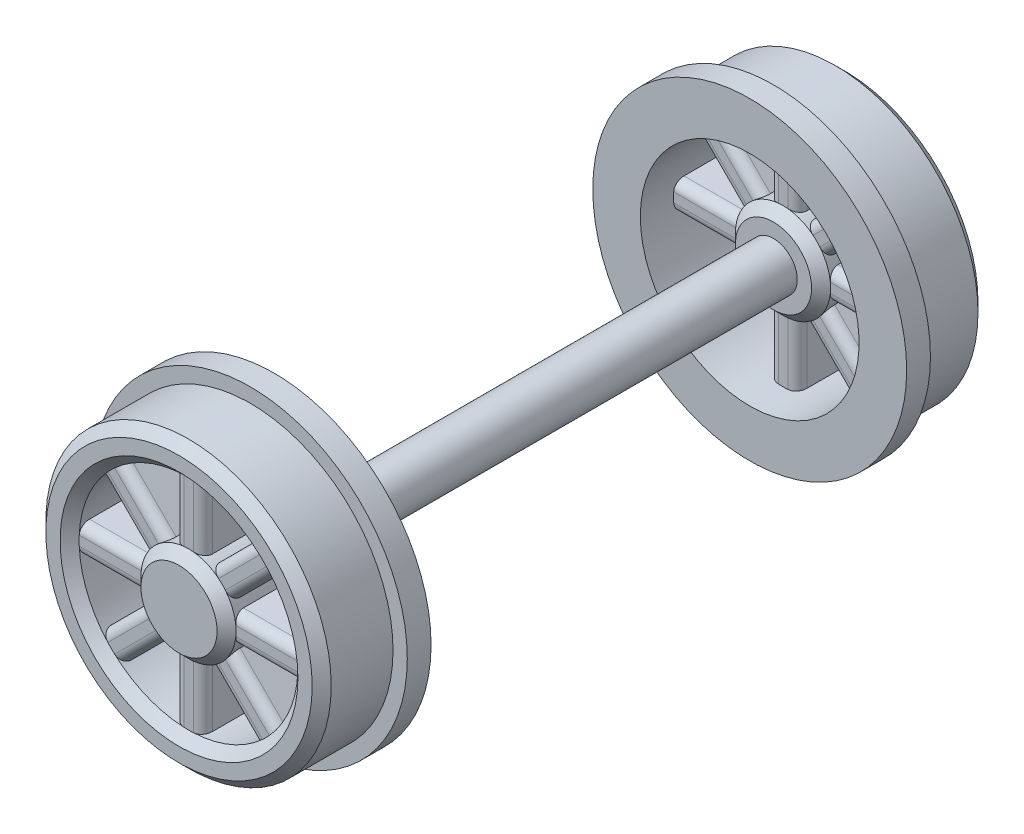
SolidWorks part; units mm, degrees
ref_plane "Front Plane" through (0, 0, 0) normal (0, 0, 1) x (1, 0, 0)
ref_plane "Top Plane" through (0, 0, 0) normal (0, 1, 0) x (1, 0, 0)
ref_plane "Right Plane" through (0, 0, 0) normal (1, 0, 0) x (0, 0, -1)
sketch "Master Sketch" plane through (0, 0, 0) normal (0, 0, 1) x (1, 0, 0)
  line L0 (0, 0) -> (400, 0)
  line L1 (0, 0) -> (0, 85)
  line L2 (0, 85) -> (-55, 94.698)
  line L3 (-55, 94.698) -> (-55, 99.698)
  line L4 (-55, 99.698) -> (95, 99.698)
  line L5 (95, 99.698) -> (95, 0)
  line L6 (95, 75) -> (187.5, 75)
  line L7 (187.5, 75) -> (245, 60)
  line L8 (245, 60) -> (400, 60)
  line L9 (400, 60) -> (400, 0)
  line L10 (0, 0) -> (0, -5)
  line L11 (0, -5) -> (400, -5)
  line L12 (400, -5) -> (400, 0)
  line L13 (400, 60) -> (475, 60)
  line L14 (475, 60) -> (475, 20)
  line L15 (475, -20) -> (400, -20)
  line L16 (95, 20) -> (475, 20) construction
  line L17 (475, 20) -> (475, -20)
  line L18 (460, -20) -> (460, -45)
  line L19 (460, -45) -> (535, -45)
  line L20 (535, -45) -> (600, -95)
  line L21 (600, -95) -> (525, -95)
  line L22 (525, -45) -> (525, -95)
  line L23 (525, -60) -> (0, -60)
  line L24 (0, -60) -> (0, -5)
  line L25 (245, -20) -> (400, -20)
  line L26 (187.5, -35) -> (245, -20)
  line L27 (95, -35) -> (187.5, -35)
  line L28 (95, 0) -> (95, -35)
  line L29 (95, -35) -> (0, -32.5)
  line L30 (105, 75) -> (105, 0)
  line L31 (110, 75) -> (110, 0)
  line L32 (182.5, 75) -> (182.5, 0)
  line L33 (177.5, 75) -> (177.5, 0)
  line L34 (395, 60) -> (395, 0)
  line L35 (250, 60) -> (250, 0)
  line L36 (255, 60) -> (255, 0)
  line L37 (322.5, 60) -> (322.5, 0)
  line L38 (327.5, 60) -> (327.5, 0)
  line L39 (110, 55) -> (177.5, 55) construction
  line L40 (182.5, 55) -> (250, 55) construction
  line L41 (255, 55) -> (322.5, 55) construction
  line L42 (327.5, 55) -> (395, 55) construction
  line L43 (110, 55) -> (105, 55) construction
  line L44 (105, 55) -> (95, 55) construction
  line L45 (525, -80) -> (375, -80)
  line L46 (375, -80) -> (375, -60)
  line L47 (0, -32.5) -> (0, -122.5) construction
  line L48 (0, -122.5) -> (600, -122.5) construction
  line L49 (600, -95) -> (600, -122.5) construction
  line L50 (75, -70) -> (0, -70) construction
  line L51 (75, -70) -> (215, -70) construction
  line L52 (75, -70) -> (75, -5) construction
  line L53 (405, -92.5) -> (405, -122.5) construction
  line L54 (490, -92.5) -> (490, -122.5) construction
  line L55 (460, -20) -> (460, -5)
  line L56 (460, -5) -> (400, -5)
  line L57 (395, 0) -> (395, -10) construction
  line L58 (395, -10) -> (450, -10)
  line L59 (395, -10) -> (395, -45)
  line L60 (395, -45) -> (450, -45)
  line L61 (450, -10) -> (450, -45)
  line L62 (422.5, -61) -> (382.5, -61) construction
  line L63 (382.5, -33.5) -> (462.5, -33.5)
  line L64 (382.5, -33.5) -> (382.5, -88.5)
  line L65 (382.5, -88.5) -> (462.5, -88.5)
  line L66 (462.5, -33.5) -> (462.5, -88.5)
  line L67 (422.5, -61) -> (422.5, -45) construction
  line L68 (395, -45) -> (422.5, -61) construction
  line L69 (422.5, -61) -> (450, -45) construction
  line L70 (422.5, -61) -> (462.5, -61) construction
  line L71 (437.5, 60) -> (437.5, 170) construction
  line L72 (437.5, 170) -> (462.5, 170)
  line L73 (462.5, 170) -> (497.5, 145)
  line L74 (497.5, 145) -> (492.5, 145)
  line L75 (492.5, 145) -> (492.5, 125)
  line L76 (437.5, 60) -> (457.5, 60)
  line L77 (457.5, 60) -> (457.5, 80) construction
  line L78 (457.5, 80) -> (492.5, 125)
  line L79 (437.5, 170) -> (437.5, 60)
  line L80 (288.75, 55) -> (288.75, 60) construction
  line L81 (288.75, 60) -> (288.75, 96) construction
  line L82 (313.75, 60) -> (313.75, 66)
  line L83 (313.75, 68) -> (308.75, 73)
  line L84 (308.75, 73) -> (308.75, 88)
  line L85 (308.75, 88) -> (310.75, 90)
  line L86 (310.75, 92) -> (309.25, 92)
  line L87 (288.75, 96) -> (300.75, 96)
  line L88 (313.75, 68) -> (313.75, 66) construction
  line L89 (310.75, 92) -> (310.75, 90) construction
  line L90 (288.75, 96) -> (288.75, 60)
  line L91 (288.75, 96) -> (288.75, 100)
  line L92 (288.75, 100) -> (289.75, 100)
  line L93 (289.75, 100) -> (289.75, 98.5) construction
  line L94 (289.75, 98.5) -> (291.25, 98.5) construction
  line L95 (291.25, 98.5) -> (291.25, 97.5) construction
  line L96 (291.25, 97.5) -> (292.75, 96) construction
  line L97 (291.25, 97.5) -> (292.75, 96)
  line L98 (361.25, 55) -> (361.25, 60) construction
  line L99 (361.25, 60) -> (361.25, 100) construction
  line L100 (361.25, 100) -> (289.75, 100) construction
  line L101 (300.75, 96) -> (361.25, 96) construction
  line L102 (361.25, 96) -> (363.75, 96)
  line L103 (363.75, 96) -> (363.75, 66)
  line L104 (363.75, 66) -> (358.75, 66)
  line L105 (358.75, 66) -> (358.75, 96)
  line L106 (358.75, 96) -> (361.25, 96)
  line L107 (363.75, 66) -> (363.75, 63.5) construction
  line L108 (363.75, 63.5) -> (366.25, 63.5) construction
  line L109 (366.25, 63.5) -> (366.25, 62.5) construction
  line L110 (366.25, 62.5) -> (369.25, 60)
  line L111 (361.25, 60) -> (361.25, 66)
  line L112 (143.75, 55) -> (143.75, 75) construction
  line L113 (143.75, 75) -> (143.75, 115)
  line L114 (168.75, 75) -> (168.75, 81)
  line L115 (168.75, 81) -> (168.75, 83) construction
  line L116 (168.75, 83) -> (163.75, 88)
  line L117 (163.75, 88) -> (163.75, 107)
  line L118 (163.75, 107) -> (165.75, 109)
  line L119 (165.75, 109) -> (165.75, 111) construction
  line L120 (165.75, 111) -> (164.25, 111)
  line L121 (143.75, 115) -> (155.75, 115)
  line L122 (308.75, 88) -> (288.75, 88) construction
  line L123 (163.75, 107) -> (143.75, 107) construction
  line L124 (143.75, 115) -> (143.75, 119)
  line L125 (143.75, 119) -> (144.75, 119)
  line L126 (144.75, 119) -> (144.75, 117.5) construction
  line L127 (144.75, 117.5) -> (146.25, 117.5) construction
  line L128 (146.25, 117.5) -> (146.25, 116.5) construction
  line L129 (146.25, 116.5) -> (147.75, 115)
  line L130 (55, -70) -> (29.5, -70) construction
  line L131 (24.75, -67) -> (29.5, -70) construction
  line L132 (24.75, -73) -> (59.75, -73)
  line L133 (24.75, -73) -> (24.75, -67)
  line L134 (24.75, -67) -> (59.75, -67)
  line L135 (59.75, -73) -> (59.75, -67)
  line L136 (24.75, -73) -> (59.75, -67) construction
  line L137 (24.75, -67) -> (59.75, -73) construction
  line L138 (55, -70) -> (59.75, -67) construction
  line L139 (29.9822, -47.4731) -> (32.9822, -42.2769)
  line L140 (29.9822, -47.4731) -> (60.2931, -64.9731)
  line L141 (60.2931, -64.9731) -> (63.2931, -59.7769)
  line L142 (32.9822, -42.2769) -> (63.2931, -59.7769)
  line L143 (29.9822, -47.4731) -> (63.2931, -59.7769) construction
  line L144 (75, -70) -> (10.0481, -32.5) construction
  line L145 (32.9822, -42.2769) -> (60.2931, -64.9731) construction
  line L146 (47.2769, -27.9822) -> (52.4731, -24.9822)
  line L147 (47.2769, -27.9822) -> (64.7769, -58.2931)
  line L148 (64.7769, -58.2931) -> (69.9731, -55.2931)
  line L149 (52.4731, -24.9822) -> (69.9731, -55.2931)
  line L150 (47.2769, -27.9822) -> (69.9731, -55.2931) construction
  line L151 (75, -70) -> (37.5, -5.0481) construction
  line L152 (52.4731, -24.9822) -> (64.7769, -58.2931) construction
  line L153 (72, -19.75) -> (78, -19.75)
  line L154 (72, -19.75) -> (72, -54.75)
  line L155 (72, -54.75) -> (78, -54.75)
  line L156 (78, -19.75) -> (78, -54.75)
  line L157 (72, -19.75) -> (78, -54.75) construction
  line L158 (75, -70) -> (75, 5) construction
  line L159 (78, -19.75) -> (72, -54.75) construction
  line L160 (97.5269, -24.9822) -> (102.7231, -27.9822)
  line L161 (97.5269, -24.9822) -> (80.0269, -55.2931)
  line L162 (80.0269, -55.2931) -> (85.2231, -58.2931)
  line L163 (102.7231, -27.9822) -> (85.2231, -58.2931)
  line L164 (97.5269, -24.9822) -> (85.2231, -58.2931) construction
  line L165 (75, -70) -> (112.5, -5.0481) construction
  line L166 (102.7231, -27.9822) -> (80.0269, -55.2931) construction
  line L171 (0, 85) -> (8, 85) construction
  line L172 (75, -70) -> (139.9519, -32.5) construction
  line L173 (402, -117.5) -> (408, -117.5)
  line L178 (402, -117.5) -> (402, -97.5)
  line L179 (75, -70) -> (150, -70) construction
  line L180 (402, -97.5) -> (408, -97.5)
  line L185 (408, -117.5) -> (408, -97.5)
  line L186 (75, -70) -> (139.9519, -107.5) construction
  line L187 (402, -117.5) -> (408, -97.5) construction
  line L188 (102.7231, -112.0178) -> (97.5269, -115.0178)
  line L189 (102.7231, -112.0178) -> (85.2231, -81.7069)
  line L190 (85.2231, -81.7069) -> (80.0269, -84.7069)
  line L191 (97.5269, -115.0178) -> (80.0269, -84.7069)
  line L192 (102.7231, -112.0178) -> (80.0269, -84.7069) construction
  line L193 (75, -70) -> (112.5, -134.9519) construction
  line L194 (97.5269, -115.0178) -> (85.2231, -81.7069) construction
  line L195 (78, -120.25) -> (72, -120.25)
  line L196 (78, -120.25) -> (78, -85.25)
  line L197 (78, -85.25) -> (72, -85.25)
  line L198 (72, -120.25) -> (72, -85.25)
  line L199 (78, -120.25) -> (72, -85.25) construction
  line L200 (75, -70) -> (75, -145) construction
  line L201 (72, -120.25) -> (78, -85.25) construction
  line L202 (52.4731, -115.0178) -> (47.2769, -112.0178)
  line L203 (52.4731, -115.0178) -> (69.9731, -84.7069)
  line L204 (69.9731, -84.7069) -> (64.7769, -81.7069)
  line L205 (47.2769, -112.0178) -> (64.7769, -81.7069)
  line L206 (52.4731, -115.0178) -> (64.7769, -81.7069) construction
  line L207 (75, -70) -> (37.5, -134.9519) construction
  line L208 (47.2769, -112.0178) -> (69.9731, -84.7069) construction
  line L209 (32.9822, -97.7231) -> (29.9822, -92.5269)
  line L210 (32.9822, -97.7231) -> (63.2931, -80.2231)
  line L211 (63.2931, -80.2231) -> (60.2931, -75.0269)
  line L212 (29.9822, -92.5269) -> (60.2931, -75.0269)
  line L213 (32.9822, -97.7231) -> (60.2931, -75.0269) construction
  line L214 (75, -70) -> (10.0481, -107.5) construction
  line L215 (29.9822, -92.5269) -> (63.2931, -80.2231) construction
  line L216 (117.0178, -42.2769) -> (120.0178, -47.4731)
  line L217 (120.0178, -47.4731) -> (89.7069, -64.9731)
  line L218 (86.7069, -59.7769) -> (89.7069, -64.9731)
  line L219 (117.0178, -42.2769) -> (86.7069, -59.7769)
  line L220 (117.0178, -42.2769) -> (89.7069, -64.9731) construction
  line L221 (120.0178, -47.4731) -> (86.7069, -59.7769) construction
  line L222 (125.25, -67) -> (125.25, -73)
  line L223 (125.25, -73) -> (90.25, -73)
  line L224 (90.25, -67) -> (90.25, -73)
  line L225 (125.25, -67) -> (90.25, -67)
  line L226 (120.0178, -92.5269) -> (117.0178, -97.7231)
  line L227 (117.0178, -97.7231) -> (86.7069, -80.2231)
  line L228 (89.7069, -75.0269) -> (86.7069, -80.2231)
  line L229 (120.0178, -92.5269) -> (89.7069, -75.0269)
  line L230 (120.0178, -92.5269) -> (86.7069, -80.2231) construction
  line L231 (117.0178, -97.7231) -> (89.7069, -75.0269) construction
  line L232 (125.25, -73) -> (90.25, -67) construction
  line L233 (125.25, -67) -> (90.25, -73) construction
  line L234 (402, -97.5) -> (408, -117.5) construction
  line L235 (8, 27) -> (87, 27)
  line L236 (8, 27) -> (8, 8)
  line L237 (8, 8) -> (87, 8)
  line L238 (87, 27) -> (87, 8)
  line L239 (8, 85) -> (43.5, 85)
  line L240 (8, 85) -> (8, 35)
  line L241 (8, 35) -> (43.5, 35)
  line L242 (43.5, 85) -> (43.5, 35)
  line L243 (51.5, 85) -> (87, 85)
  line L244 (51.5, 85) -> (51.5, 35)
  line L245 (51.5, 35) -> (87, 35)
  line L246 (87, 85) -> (87, 35)
  line L247 (8, 33) -> (87, 33)
  line L248 (8, 33) -> (8, 31)
  line L249 (8, 31) -> (87, 31)
  line L250 (87, 33) -> (87, 31)
  line L251 (485, 100) -> (496.6667, 115)
  line L252 (485, 60) -> (515, 60)
  line L253 (485, 60) -> (485, 100)
  line L254 (485, 100) -> (515, 100)
  line L255 (515, 60) -> (515, 100)
  line L256 (496.6667, 115) -> (503.3333, 115)
  line L257 (503.3333, 115) -> (515, 100)
  line L258 (475, 60) -> (485, 60)
  line L259 (515, 60) -> (515, 55)
  line L260 (515, 55) -> (475, 55)
  line L261 (500, 115) -> (500, 117) construction
  line L262 (500, 117) -> (500, 119) construction
  line L263 (494, 115) -> (506, 115)
  line L264 (494, 115) -> (494, 117)
  line L265 (494, 117) -> (506, 117)
  line L266 (506, 115) -> (506, 117)
  line L267 (494, 115) -> (506, 117) construction
  line L268 (494, 117) -> (506, 115) construction
  line L269 (500, 115) -> (500, 100) construction
  line L270 (457.5, 80) -> (457.5, 64)
  line L271 (457.5, 64) -> (458.5, 64)
  line L272 (458.5, 64) -> (458.5, 62)
  line L273 (458.5, 62) -> (455.5, 62)
  line L274 (455.5, 62) -> (455.5, 60)
  circle A0 centre (75, -70) radius 52.5
  circle A1 centre (215, -70) radius 52.5
  circle A2 centre (405, -92.5) radius 30
  circle A3 centre (490, -92.5) radius 30
  arc A4 (313.75, 68) -> (313.75, 66) centre (313.75, 67) cw
  arc A5 (310.75, 92) -> (310.75, 90) centre (310.75, 91) cw
  arc A6 (300.75, 96) -> (309.25, 92) centre (300.75, 84.9687) cw
  arc A7 (289.75, 100) -> (291.25, 98.5) centre (289.75, 98.5) cw
  arc A8 (291.25, 98.5) -> (291.25, 97.5) centre (291.25, 98) cw
  arc A9 (363.75, 66) -> (366.25, 63.5) centre (363.75, 63.5) cw
  arc A10 (366.25, 63.5) -> (366.25, 62.5) centre (366.25, 63) cw
  arc A11 (155.75, 115) -> (164.25, 111) centre (155.75, 103.9687) cw
  arc A12 (144.75, 119) -> (146.25, 117.5) centre (144.75, 117.5) cw
  arc A13 (146.25, 117.5) -> (146.25, 116.5) centre (146.25, 117) cw
  circle A14 centre (75, -70) radius 45.5
  circle A15 centre (215, -70) radius 45.5
  circle A16 centre (405, -92.5) radius 23
  circle A17 centre (490, -92.5) radius 23
  circle A18 centre (405, -92.5) radius 10
  circle A19 centre (490, -92.5) radius 10
  circle A20 centre (75, -70) radius 20
  circle A21 centre (215, -70) radius 20
  arc A22 (515, 55) -> (475, 15) centre (515, 15) ccw
  circle A23 centre (500, 119) radius 4
  circle A24 centre (500, 119) radius 4.25
  point P168 (42.25, -70)
  point P174 (405, -107.5)
  point P230 (75, -70)
  point P286 (500, 116)
  dimension "D63" = 1
  dimension "D95" = 7
  dimension "D96" = 7
  dimension "D97" = 7
  dimension "D98" = 7
  dimension "D99" = 20
  dimension "D100" = 20
  dimension "D101" = 40
  dimension "D102" = 40
  dimension "D127" = 8
  dimension "D129" = 8.5
  dimension "D1" = 400
  dimension "D2" = 85
  dimension "D3" = 100
  dimension "D4" = 5
  dimension "D5" = 55
  dimension "D6" = 150
  dimension "D7" = 5
  dimension "D8" = 5
  dimension "D9" = 5
  dimension "D10" = 5
  dimension "D11" = 5
  dimension "D12" = 10
  dimension "D13" = 5
  dimension "D14" = 5
  dimension "D15" = 75
  dimension "D16" = 75
  dimension "D17" = 60
  dimension "D18" = 20
  dimension "D19" = 40
  dimension "D20" = 25
  dimension "D21" = 15
  dimension "D22" = 75
  dimension "D23" = 50
  dimension "D24" = 75
  dimension "D25" = 10
  dimension "D26" = 15
  dimension "D27" = 150
  dimension "D28" = 20
  dimension "D29" = 90
  dimension "D30" = 5
  dimension "D31" = 65
  dimension "D32" = 75
  dimension "D33" = 140
  dimension "D34" = 85
  dimension "D35" = 30
  dimension "D36" = 30
  dimension "D37" = 110
  dimension "D38" = 5
  dimension "D39" = 10
  dimension "D40" = 16
  dimension "D41" = 80
  dimension "D42" = 55
  dimension "D43" = 110
  dimension "D44" = 25
  dimension "D45" = 20
  dimension "D46" = 20
  dimension "D47" = 20
  dimension "D48" = 25
  dimension "D49" = 5
  dimension "D50" = 35
  dimension "D51" = 25
  dimension "D52" = 6
  dimension "D53" = 5
  dimension "D54" = 2
  dimension "D55" = 15
  dimension "D56" = 5
  dimension "D57" = 2
  dimension "D58" = 2
  dimension "D59" = 1.5
  dimension "D60" = 36
  dimension "D61" = 12
  dimension "D62" = 2
  dimension "D64" = 4
  dimension "D65" = 1.5
  dimension "D66" = 1.5
  dimension "D67" = 2.5
  dimension "D68" = 1
  dimension "D69" = 1.5
  dimension "D70" = 5
  dimension "D71" = 2.5
  dimension "D72" = 30
  dimension "D73" = 2.5
  dimension "D74" = 2.5
  dimension "D75" = 1
  dimension "D76" = 3
  dimension "D77" = 40
  dimension "D78" = 6
  dimension "D79" = 25
  dimension "D80" = 2
  dimension "D81" = 5
  dimension "D82" = 5
  dimension "D83" = 2
  dimension "D84" = 2
  dimension "D85" = 2
  dimension "D86" = 1.5
  dimension "D87" = 8
  dimension "D88" = 12
  dimension "D89" = 1
  dimension "D90" = 1.5
  dimension "D91" = 1.5
  dimension "D92" = 1.5
  dimension "D93" = 1.5
  dimension "D94" = 4
  dimension "D103" = 6
  dimension "D104" = 35
  dimension "D106" = 6
  dimension "D107" = 20
  dimension "D108" = 8
  dimension "D109" = 8
  dimension "D110" = 8
  dimension "D111" = 8
  dimension "D112" = 8
  dimension "D113" = 8
  dimension "D114" = 2
  dimension "D115" = 8
  dimension "D116" = 8
  dimension "D117" = 4
  dimension "D118" = 5
  dimension "D119" = 2
  dimension "D120" = 50
  dimension "D121" = 40
  dimension "D122" = 30
  dimension "D123" = 40
  dimension "D124" = 15
  dimension "D125" = 12
  dimension "D126" = 2
  dimension "D128" = 2
  dimension "D130" = 16
  dimension "D131" = 2
  dimension "D132" = 3
  dimension "D133" = 1
  dimension "D105" = 12
sketch "Sketch438" plane through (0, 0, 0) normal (0, 0, 1) x (1, 0, 0)
  circle A0 centre (405, -92.5) radius 23 construction
  circle A1 centre (405, -92.5) radius 30 construction
  circle A2 centre (405, -92.5) radius 23
  circle A3 centre (405, -92.5) radius 30
  circle A4 centre (405, -92.5) radius 10 construction
  circle A5 centre (405, -92.5) radius 10
extrude "Boss-Extrude1" add sketch "Sketch438" along normal blind 15 contours A5 | A3 A2 region at (375.8485, -92.5, 0) region at (405, -92.5, 0)
sketch "Sketch439" plane through (0, 0, 15) normal (0, 0, 1) x (1, 0, 0)
  line L0 (402, -117.5) -> (408, -117.5) construction
  line L1 (408, -117.5) -> (408, -97.5) construction
  line L2 (402, -97.5) -> (408, -97.5) construction
  line L3 (402, -117.5) -> (402, -97.5) construction
  line L4 (402, -117.5) -> (408, -117.5)
  line L5 (408, -117.5) -> (408, -97.5)
  line L6 (402, -97.5) -> (408, -97.5)
  line L7 (402, -117.5) -> (402, -97.5)
extrude "Boss-Extrude2" add sketch "Sketch439" against normal blind 11 from offset 2 offset against normal yes
fillet "Fillet1" radius 2 4 edges at (408, -108.6715, 2) (408, -108.6715, 13) (402, -108.6715, 13) (402, -108.6715, 2)
pattern_circular "CirPattern1" count 8 over 360 about axis through (405, -92.5, 15) along (0, 0, 1) of "Fillet1", "Boss-Extrude2"
chamfer "Chamfer1" distance 2 angle 45 4 edges at (435, -92.5, 15) (428, -92.5, 15) (415, -92.5, 0) (415, -92.5, 15)
sketch "Sketch440" plane through (0, 0, 0) normal (0, 0, -1) x (-1, 0, 0)
  circle A0 centre (-405, -92.5) radius 23 construction
  circle A1 centre (-405, -92.5) radius 23
  circle A2 centre (-405, -92.5) radius 33
  dimension "D1" = 66
extrude "Boss-Extrude3" add sketch "Sketch440" along normal blind 5
sketch "Sketch441" plane through (0, 0, 0) normal (0, 0, -1) x (-1, 0, 0)
  line L0 (-405, -84.5) -> (-405, -100.5) construction
  circle A0 centre (-405, -92.5) radius 8 construction
  circle A1 centre (-405, -92.5) radius 5
  dimension "D1" = 10
extrude "Boss-Extrude4" add sketch "Sketch441" along normal blind 55
mirror "Mirror1" about plane through (405, -92.5, -55) normal (0, 0, -1) of bodies 298
